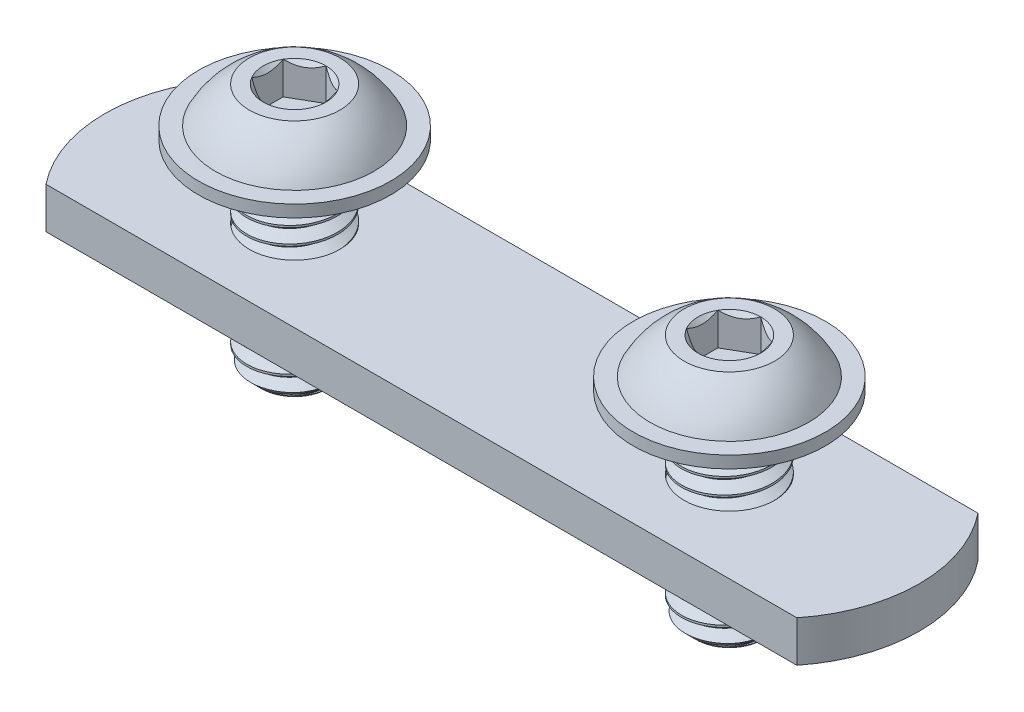
SolidWorks part; units mm, degrees
ref_plane "Front Plane" through (0, 0, 0) normal (0, 0, 1) x (1, 0, 0)
ref_plane "Top Plane" through (0, 0, 0) normal (0, 1, 0) x (1, 0, 0)
ref_plane "Right Plane" through (0, 0, 0) normal (1, 0, 0) x (0, 0, -1)
sketch "Sketch1" plane through (0, 0, 0) normal (0, 1, 0) x (1, 0, 0)
  line L0 (-19.05, 0) -> (19.05, 0) construction
  circle A0 centre (-19.05, 0) radius 3.9688
  point P3 (-23.0188, 0)
  point P4 (-15.0813, 0)
  dimension "D1" = 7.9375
  dimension "D2" = 38.1
extrude "Boss-Extrude1" add sketch "Sketch1" against normal blind 17.4625
sketch "Sketch2" plane through (0, -17.4625, 0) normal (0, -1, 0) x (1, 0, 0)
  circle A1 centre (-19.05, 0) radius 3.9688
  circle A2 centre (-19.05, 0) radius 3.9688
  point P0 (-19.05, -3.9688)
  dimension "D1" = 0
curve "Helix/Spiral1" pitch 1.4111 height 18.8736 turns 13.375
ref_plane "Plane1" through (-19.05, 0, 0) normal (1, 0, 0) x (0, 0, -1)
sketch "Sketch3" plane through (-19.05, 0, 0) normal (1, 0, 0) x (0, 0, -1)
  line L0 (4.1215, -17.3743) -> (2.8994, -18.0799) construction
  line L1 (2.8994, -18.0799) -> (4.1215, -18.7854) construction
  line L2 (4.1215, -18.7854) -> (4.1215, -17.3743) construction
  line L3 (3.0522, -17.9917) -> (3.0522, -18.1681) construction
  line L4 (3.9688, -17.4625) -> (3.9688, -18.6972) construction
  line L5 (2.8994, -18.0799) -> (3.0522, -18.0799) construction
  line L6 (3.9688, -18.0799) -> (4.1215, -18.0799) construction
  line L8 (2.8994, -18.0799) -> (-3.9688, -18.0799) construction
  line L9 (3.0522, -17.9917) -> (4.0451, -17.4184)
  line L10 (3.0522, -17.9917) -> (3.0522, -18.1681)
  line L11 (3.0522, -18.1681) -> (4.0451, -18.7413)
  line L12 (4.0451, -18.7413) -> (4.0451, -17.4184)
  line L14 (-3.9688, -18.0799) -> (-3.9688, -16.6687) construction
  line L15 (-3.9688, -16.6687) -> (-3.9688, -15.2576) construction
  line L16 (-3.9688, -15.2576) -> (-3.9687, -13.8465) construction
  line L17 (-3.9687, -13.8465) -> (-3.9688, -12.4354) construction
  line L18 (-3.9688, 0) -> (-3.9688, -17.4625) construction
  point P15 (4.0451, -18.0799)
  dimension "D1" = 1.4111
  dimension "D2" = 0.1764
sweep "Cut-Sweep1" cut profiles "Sketch3" path "Helix/Spiral1"
sketch "Sketch4" plane through (0, -17.4625, 0) normal (0, -1, 0) x (1, 0, 0)
  circle A0 centre (-19.05, 0) radius 2.8994
extrude "Cut-Extrude1" cut sketch "Sketch4" against normal blind 1.4111 draft 45 flip side to cut
sketch "Sketch5" plane through (0, 0, 0) normal (0, 0, 1) x (1, 0, 0)
  line L0 (-19.05, 0) -> (-19.05, 4.2164)
  line L1 (-27.4701, 0) -> (-19.05, 0)
  line L2 (-19.05, 4.2164) -> (-23.0188, 4.2164)
  line L3 (-25.9969, 1.0541) -> (-27.4701, 1.0541)
  line L4 (-27.4701, 1.0541) -> (-27.4701, 0)
  line L5 (-19.05, 0) -> (-19.05, -17.4625) construction
  arc A0 (-23.0188, 4.2164) -> (-25.9969, 1.0541) centre (-19.05, -2.5047) ccw
  dimension "D1" = 4.2164
  dimension "D2" = 1.0541
  dimension "D3" = 16.8402
  dimension "D4" = 13.8938
revolve "Revolve1" add sketch "Sketch5" angle 360 about L0
sketch "Sketch6" plane through (0, 4.2164, 0) normal (0, 1, 0) x (1, 0, 0)
  line L1 (-19.05, 2.7496) -> (-21.4313, 1.3748)
  line L2 (-21.4313, 1.3748) -> (-21.4312, -1.3748)
  line L3 (-21.4312, -1.3748) -> (-19.05, -2.7496)
  line L4 (-19.05, -2.7496) -> (-16.6688, -1.3748)
  line L5 (-16.6688, -1.3748) -> (-16.6688, 1.3748)
  line L6 (-16.6688, 1.3748) -> (-19.05, 2.7496)
  circle A0 centre (-19.05, 0) radius 2.3813 construction
  dimension "D1" = 4.7625
extrude "Cut-Extrude2" cut sketch "Sketch6" against normal blind 2.8575
sketch "Sketch7" plane through (0, 4.2164, 0) normal (0, 1, 0) x (1, 0, 0)
  circle A0 centre (-19.05, 0) radius 2.7496
extrude "Cut-Extrude3" cut sketch "Sketch7" against normal blind 2.8575 draft 45
move or copy body "Body-Move/Copy1" bodies to move or copy 110 copy yes number of copies 1 translate (38.1, 0, 0)
sketch "Sketch8" plane through (0, 0, 0) normal (0, 1, 0) x (1, 0, 0)
  line L0 (-35.687, 0) -> (35.687, 0) construction
  line L2 (-32.9009, 7.9375) -> (32.9009, 7.9375)
  line L3 (-32.9009, -7.9375) -> (32.9009, -7.9375)
  line L4 (-35.687, 7.9375) -> (35.687, 7.9375) construction
  line L5 (-35.687, 7.9375) -> (-35.687, -7.9375) construction
  line L6 (-35.687, -7.9375) -> (35.687, -7.9375) construction
  line L7 (35.687, 7.9375) -> (35.687, -7.9375) construction
  arc A0 (-32.9009, 7.9375) -> (-32.9009, -7.9375) centre (-22.987, 0) ccw
  arc A1 (32.9009, 7.9375) -> (32.9009, -7.9375) centre (22.987, 0) cw
  circle A2 centre (19.05, 0) radius 3.9688
  circle A3 centre (-19.05, 0) radius 3.9688
  circle A4 centre (-19.05, 0) radius 3.9688
  dimension "D2" = 71.374
  dimension "D6" = 12.7
  dimension "D3" = 15.875
  dimension "D4" = 16.637
  dimension "D1" = 0
extrude "Boss-Extrude2" add sketch "Sketch8" against normal blind 3.6068 from offset 6.35 separate body
sketch "Sketch9" plane through (0, -9.9568, 0) normal (0, -1, 0) x (1, 0, 0)
  circle A0 centre (19.05, 0) radius 3.9688 construction
  circle A1 centre (-19.05, 0) radius 3.9688 construction
  circle A2 centre (-19.05, 0) radius 3.9688
  circle A3 centre (-19.05, 0) radius 4.5593
  circle A4 centre (19.05, 0) radius 3.9688
  circle A5 centre (19.05, 0) radius 4.5593
  dimension "D1" = 9.1186
extrude "Boss-Extrude3" add sketch "Sketch9" along normal blind 2.032
sketch "SketchZ" plane through (0, 0, 0) normal (0, 0, 1) x (1, 0, 0)
  line L0 (-15.0813, -17.7271) -> (-15.0813, -16.316) construction
  line L2 (-19.05, -18.0799) -> (-19.05, -16.6687) construction
  line L4 (-15.0813, -17.7271) -> (-19.05, -17.7271) construction
  line L5 (-19.05, -13.8465) -> (-19.05, -12.4354) construction
  line L6 (-19.05, -17.3743) -> (-19.05, -18.0799) construction
equation "\"D3@Helix/Spiral1\" = \"D4@Helix/Spiral1\" + \"D1@Boss-Extrude1\""
equation "\"D1@Sketch3\" = \"D4@Helix/Spiral1\""
equation "\"D2@Sketch3\" = \"D1@Sketch3\" / 8"
equation "\"D1@Cut-Extrude1\" = \"D4@Helix/Spiral1\""
equation "\"D1@Cut-Extrude2\" = \"D1@Sketch6\" * 3/5"
equation "\"D1@Cut-Extrude3\" = \"D1@Cut-Extrude2\""
equation "\"D2@Sketch5\" = \"D1@Sketch5\" * 1/4"
